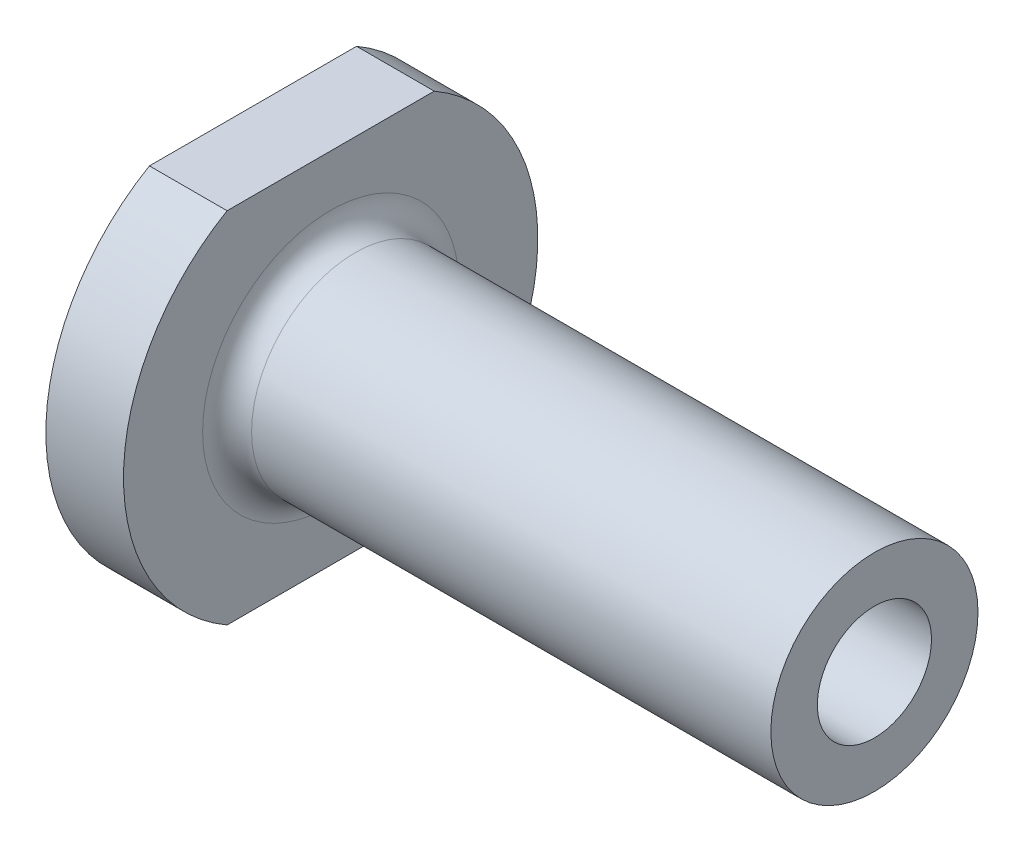
SolidWorks part; units mm, degrees
material "Ti-6Al-4VSolution treated and aged (SS)"
ref_plane "Front Plane" through (0, 0, 0) normal (0, 0, 1) x (1, 0, 0)
ref_plane "Top Plane" through (0, 0, 0) normal (0, 1, 0) x (1, 0, 0)
ref_plane "Right Plane" through (0, 0, 0) normal (1, 0, 0) x (0, 0, -1)
sketch "Sketch1" plane through (0, 0, 0) normal (0, 0, 1) x (1, 0, 0)
  line L0 (0, 0) -> (-17.6508, 0) construction
  line L1 (0, 0) -> (38.1, 0)
  line L2 (38.1, 0) -> (38.1, 6.35)
  line L3 (38.1, 6.35) -> (4.7625, 6.35)
  line L4 (4.7625, 6.35) -> (4.7625, 12.7)
  line L5 (4.7625, 12.7) -> (0, 12.7)
  line L6 (0, 12.7) -> (0, 0)
  dimension "D1" = 12.7
  dimension "D2" = 38.1
  dimension "D3" = 4.7625
  dimension "D4" = 25.4
revolve "Revolve1" add sketch "Sketch1" angle 360 about L0
fillet "Fillet1" radius 1.5 1 edges at (4.7625, 0, -6.35)
hole_wizard "5/16-18 MAKE SURE TO CHANGE THIS" positions "Sketch2" profile "Sketch3" tap size "M8x1.0" standard "ANSI Metric" end condition through all
sketch "Sketch2" plane through (38.1, 0, 0) normal (1, 0, 0) x (0, 0, -1)
  point P0 (0, 0)
sketch "Sketch3" plane through (38.1, 0, 0) normal (0, 1, 0) x (0, 0, -1)
  line L0 (0, 0) -> (0, 38.1)
  line L1 (0, 38.1) -> (3.5, 38.1)
  line L2 (3.5, 38.1) -> (3.5, 0)
  line L5 (3.5, 0) -> (0, 0)
  line L11 (0, -6.35) -> (0, 107.95) construction
  dimension "Thru Tap Drill Dia." = 7
  dimension "Thru Tap Drill Depth" = 38.1
cosmetic thread "Hole Thread1" parameters "D2"=8
sketch "Sketch4" plane through (0, 0, 0) normal (-1, 0, 0) x (0, 0, 1)
  line L0 (-6.35, 10.9985) -> (6.35, 10.9985)
  line L5 (6.35, -10.9985) -> (-6.35, -10.9985)
  arc A1 (6.35, 10.9985) -> (-6.35, 10.9985) centre (0, 0) ccw
  circle A2 centre (0, 0) radius 12.7
  arc A3 (-6.35, -10.9985) -> (6.35, -10.9985) centre (0, 0) ccw
  dimension "D1" = 0
  dimension "D2" = 12.7
extrude "Cut-Extrude1" cut sketch "Sketch4" against normal through all
